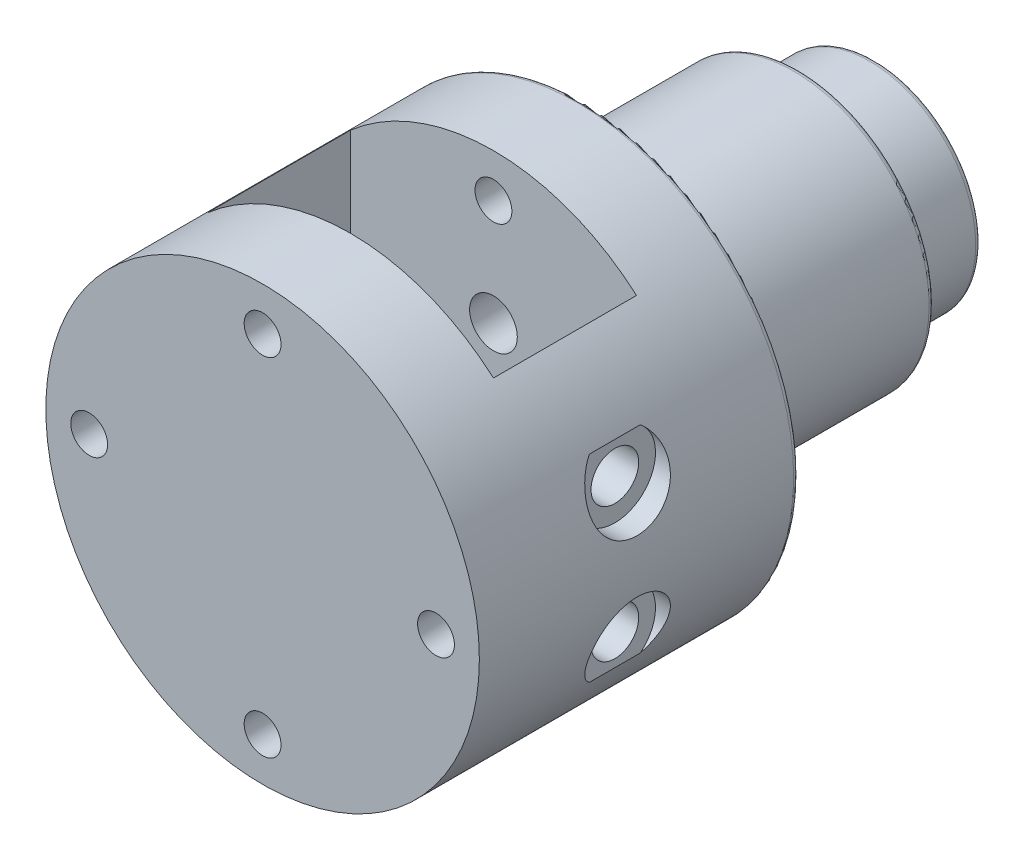
SolidWorks part; units mm, degrees
material "ABS"
ref_plane "前视基准面" through (0, 0, 0) normal (0, 0, 1) x (1, 0, 0)
ref_plane "上视基准面" through (0, 0, 0) normal (0, 1, 0) x (1, 0, 0)
ref_plane "右视基准面" through (0, 0, 0) normal (1, 0, 0) x (0, 0, -1)
sketch "草图1" plane through (0, 0, 0) normal (0, 0, 1) x (1, 0, 0)
  circle A0 centre (0, 0) radius 20
  dimension "D1" = 40
extrude "凸台-拉伸1" add sketch "草图1" along normal blind 29.5
sketch "草图2" plane through (0, 0, 0) normal (0, 1, 0) x (1, 0, 0)
  line L0 (0, 0) -> (0, -14.8) construction
  line L1 (-13.2, -21.4) -> (13.2, -21.4)
  line L2 (-13.2, -21.4) -> (-13.2, -8.2)
  line L3 (-13.2, -8.2) -> (13.2, -8.2)
  line L4 (13.2, -21.4) -> (13.2, -8.2)
  line L5 (-13.2, -21.4) -> (13.2, -8.2) construction
  line L6 (-13.2, -8.2) -> (13.2, -21.4) construction
  line L7 (-20, -29.5) -> (20, -29.5) construction
  point P0 (0, -14.8)
  dimension "D1" = 26.4
  dimension "D2" = 13.2
  dimension "D3" = 8.1
extrude "切除-拉伸1" cut sketch "草图2" against normal blind 30 and the other way blind 30
sketch "草图4" plane through (0, 0, 0) normal (0, 0, -1) x (-1, 0, 0)
  line L0 (0, 0) -> (0, 16) construction
  circle A0 centre (0, 16) radius 1.7
  circle A1 centre (16, 0) radius 1.7
  circle A2 centre (0, -16) radius 1.7
  circle A3 centre (-16, 0) radius 1.7
  dimension "D2" = 3.4
  dimension "D1" = 16
  dimension "D3" = 4
extrude "切除-拉伸3" cut sketch "草图4" against normal through all
sketch "草图5" plane through (0, 0, 0) normal (0, 0, -1) x (-1, 0, 0)
  circle A0 centre (0, 0) radius 12.5
  dimension "D1" = 25
extrude "凸台-拉伸2" add sketch "草图5" along normal blind 20
sketch "草图6" plane through (0, 0, -20) normal (0, 0, -1) x (-1, 0, 0)
  circle A0 centre (0, 0) radius 9.8
  dimension "D1" = 19.6
extrude "凸台-拉伸3" add sketch "草图6" along normal blind 7
sketch "草图7" plane through (0, 0, -27) normal (0, 0, -1) x (-1, 0, 0)
  line L0 (0, 6.2) -> (0, -6.2) construction
  circle A0 centre (0, 6.2) radius 2.2
  circle A1 centre (0, -6.2) radius 2.2
  dimension "D1" = 4.4
  dimension "D2" = 4.4
  dimension "D3" = 12.4
extrude "切除-拉伸7" cut sketch "草图7" against normal up to next
sketch "草图8" plane through (-13.2, 0, 0) normal (1, 0, 0) x (0, 0, -1)
  line L0 (-14.8, 15.0253) -> (-14.8, -15.0253) construction
  line L3 (-21.4, 15.0253) -> (-8.2, 15.0253) construction
  line L5 (-8.2, -15.0253) -> (-21.4, -15.0253) construction
  circle A0 centre (-14.8, 6.2) radius 2.2
  circle A1 centre (-14.8, -6.2) radius 2.2
  point P10 (-14.8, 0)
  point P13 (-14.8, 15.0253)
  dimension "D1" = 4.4
  dimension "D2" = 4.4
  dimension "D3" = 12.4
  dimension "D4" = 6.2
extrude "切除-拉伸8" cut sketch "草图8" against normal through all and the other way through all
sketch "草图9" plane through (-13.2, 0, 0) normal (1, 0, 0) x (0, 0, -1)
  circle A1 centre (-14.8, 6.2) radius 3.75
  circle A2 centre (-14.8, -6.2) radius 3.75
  dimension "D1" = 7.5
  dimension "D2" = 7.5
extrude "切除-拉伸9" cut sketch "草图9" against normal blind 10 from offset 5 offset against normal yes
sketch "草图10" plane through (-13.2, 0, 0) normal (1, 0, 0) x (0, 0, -1)
  circle A0 centre (-14.8, 6.2) radius 3.75
  circle A1 centre (-14.8, -6.2) radius 3.75
  dimension "D1" = 7.5
  dimension "D2" = 7.5
extrude "切除-拉伸10" cut sketch "草图10" along normal blind 10 from offset 31
fillet "圆角1" radius 0.5 3 edges at (-9.8, 0, -27) (-12.5, 0, -20) (20, 0, 0)
fillet "圆角2" radius 1 1 edges at (12.5, 0, 0)
